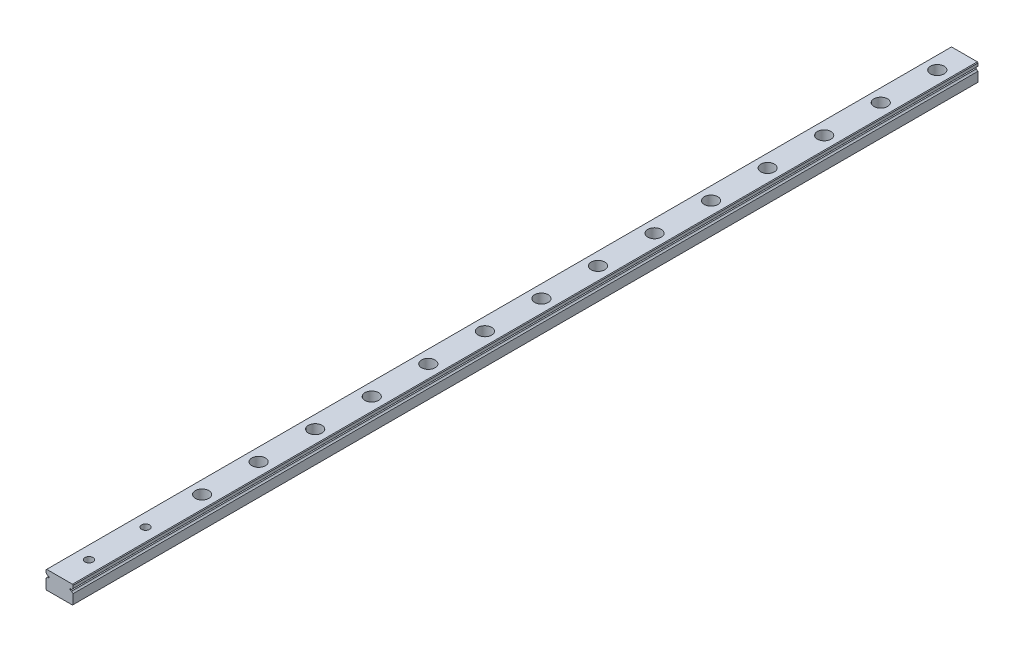
SolidWorks part; units mm, degrees
ref_plane "Спереди" through (0, 0, 0) normal (0, 0, 1) x (1, 0, 0)
ref_plane "Сверху" through (0, 0, 0) normal (0, 1, 0) x (1, 0, 0)
ref_plane "Справа" through (0, 0, 0) normal (1, 0, 0) x (0, 0, -1)
sketch "Эскиз1" plane through (0, 0, 0) normal (0, 0, 1) x (1, 0, 0)
  line L0 (-6, 3.7) -> (-5.7, 4)
  line L1 (-5.7, -4) -> (5.7, -4)
  line L2 (-6, -3.7) -> (-6, 0.549)
  line L3 (-5.7, 4) -> (5.7, 4)
  line L4 (6, -3.7) -> (6, 0.549)
  line L5 (-6, -4) -> (6, 4) construction
  line L6 (-6, 4) -> (6, -4) construction
  line L7 (-6, -3.7) -> (-5.7, -4)
  line L8 (5.7, -4) -> (6, -3.7)
  line L9 (5.7, 4) -> (6, 3.7)
  line L10 (-6, 2.451) -> (-6, 3.7)
  line L11 (-5.3546, 1.7981) -> (-4.6435, 1.7981)
  line L12 (0, 5.4188) -> (0, -5.747) construction
  line L13 (-5.3546, 1.2019) -> (-4.6435, 1.2019)
  line L14 (-4.6435, 1.7981) -> (-4.6435, 1.2019)
  line L15 (4.6435, 1.7981) -> (4.6435, 1.2019)
  line L16 (5.3546, 1.2019) -> (4.6435, 1.2019)
  line L17 (5.3546, 1.7981) -> (4.6435, 1.7981)
  line L18 (6, 2.451) -> (6, 3.7)
  line L19 (4.6435, 1.7981) -> (5.3546, 1.7981) construction
  arc A0 (-6, 0.549) -> (-5.3546, 1.2019) centre (-6.3091, 1.5) ccw
  arc A1 (-5.3546, 1.7981) -> (-6, 2.451) centre (-6.3091, 1.5) ccw
  arc A2 (5.3546, 1.7981) -> (6, 2.451) centre (6.3091, 1.5) cw
  arc A3 (6, 0.549) -> (5.3546, 1.2019) centre (6.3091, 1.5) cw
  point P0 (0, 0)
extrude "Бобышка-Вытянуть1" add sketch "Эскиз1" along normal blind 400
sketch "Эскиз2" plane through (0, 4, 0) normal (0, 1, 0) x (1, 0, 0)
  line L0 (0, 0) -> (0, -26.2396) construction
  line L1 (5.7, 0) -> (-5.7, 0) construction
  line L2 (-3.8306, -12) -> (3.8306, -12) construction
  circle A0 centre (0, -12) radius 3
  circle A1 centre (0, -12) radius 1.75
  dimension "D2" = 3.5
  dimension "D3" = 6
  dimension "D1" = 12
extrude "Вырез-Вытянуть1" cut sketch "Эскиз2" against normal blind 4.5
extrude "Вырез-Вытянуть2" cut sketch "Эскиз2<2>" against normal through all contours A1 region at (0, 4, 12)
sketch "Эскиз2<2>" plane through (0, 4, 0) normal (0, 1, 0) x (1, 0, 0) same geometry as "Эскиз2"
pattern_linear "Линейный массив1" count 14 spacing 25 along (0, 0, 1) of "Вырез-Вытянуть1", "Вырез-Вытянуть2"
sketch "Croquis1" plane through (0, 4, 0) normal (0, 1, 0) x (1, 0, 0)
  line L0 (0, -400) -> (0, -337) construction
  line L1 (5.7, -400) -> (-5.7, -400) construction
  circle A0 centre (0, -387) radius 1.75
  circle A1 centre (0, -362) radius 1.75
  dimension "D1" = 3.5
  dimension "D2" = 3.5
  dimension "D3" = 25
  dimension "D4" = 25
extrude "Cortar-Extruir1" cut sketch "Croquis1" against normal up to surface (8 mm away) up to face at (0, -4, 338.75)
